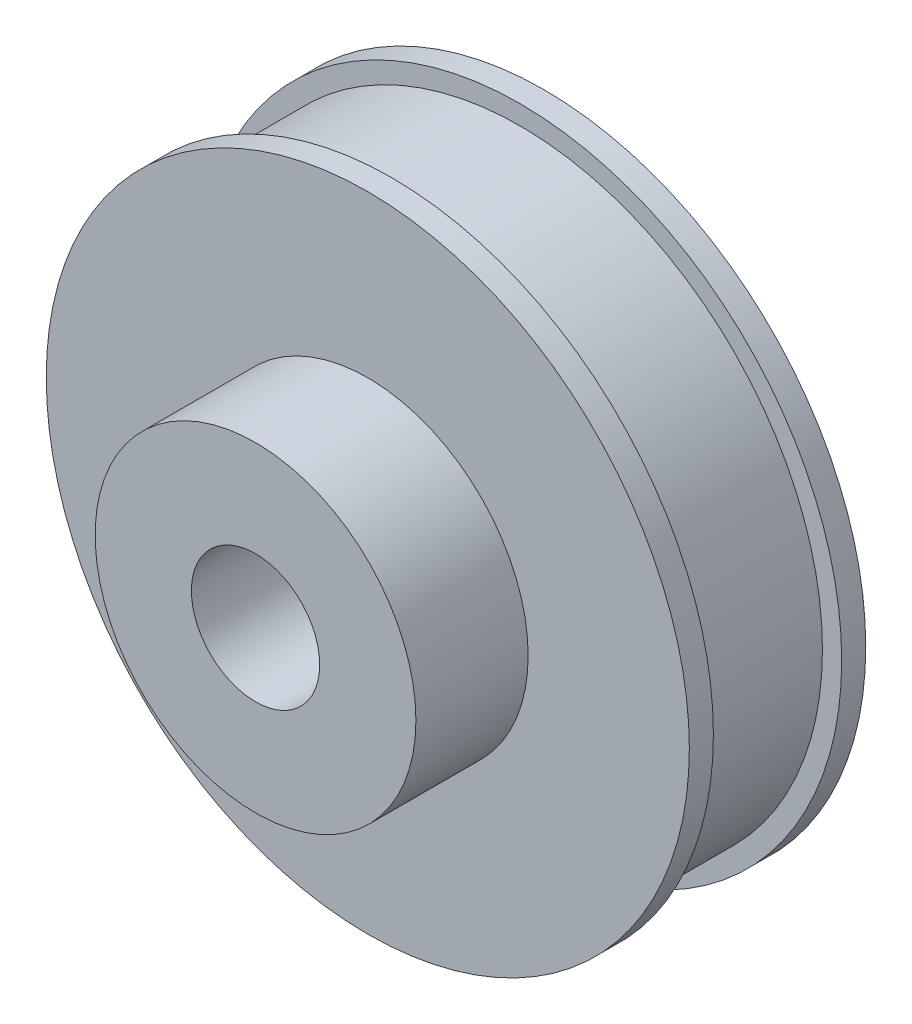
SolidWorks part; units mm, degrees
ref_plane "Front Plane" through (0, 0, 0) normal (0, 0, 1) x (1, 0, 0)
ref_plane "Top Plane" through (0, 0, 0) normal (0, 1, 0) x (1, 0, 0)
ref_plane "Right Plane" through (0, 0, 0) normal (1, 0, 0) x (0, 0, -1)
sketch "Sketch1" plane through (0, 0, 0) normal (0, 0, 1) x (1, 0, 0)
  circle A0 centre (0, 0) radius 18.85
  circle A1 centre (0, 0) radius 20.05
  circle A2 centre (0, 0) radius 10
  circle A3 centre (0, 0) radius 4
  dimension "D1" = 8
  dimension "D2" = 20
  dimension "D3" = 40.1
  dimension "D4" = 37.7
extrude "Boss-Extrude1" add sketch "Sketch1" along normal blind 11 contours A0 A2 | A2 A3 region at (-18.3168, 0, 0) region at (-9.7172, 0, 0)
extrude "Boss-Extrude2" add sketch "Sketch1<3>" along normal blind 1.5 contours A1 A0 region at (-19.4829, 0, 0)
sketch "Sketch1<3>" plane through (0, 0, 0) normal (0, 0, 1) x (1, 0, 0) same geometry as "Sketch1"
extrude "Boss-Extrude3" add sketch "Sketch1<4>" against normal blind 1.5 from offset 11 contours A1 A0 region at (-19.4829, 0, 0)
sketch "Sketch1<4>" plane through (0, 0, 0) normal (0, 0, 1) x (1, 0, 0) same geometry as "Sketch1"
extrude "Boss-Extrude4" add sketch "Sketch1<5>" along normal blind 18 contours A2 A3 region at (-9.7172, 0, 0)
sketch "Sketch1<5>" plane through (0, 0, 0) normal (0, 0, 1) x (1, 0, 0) same geometry as "Sketch1"
